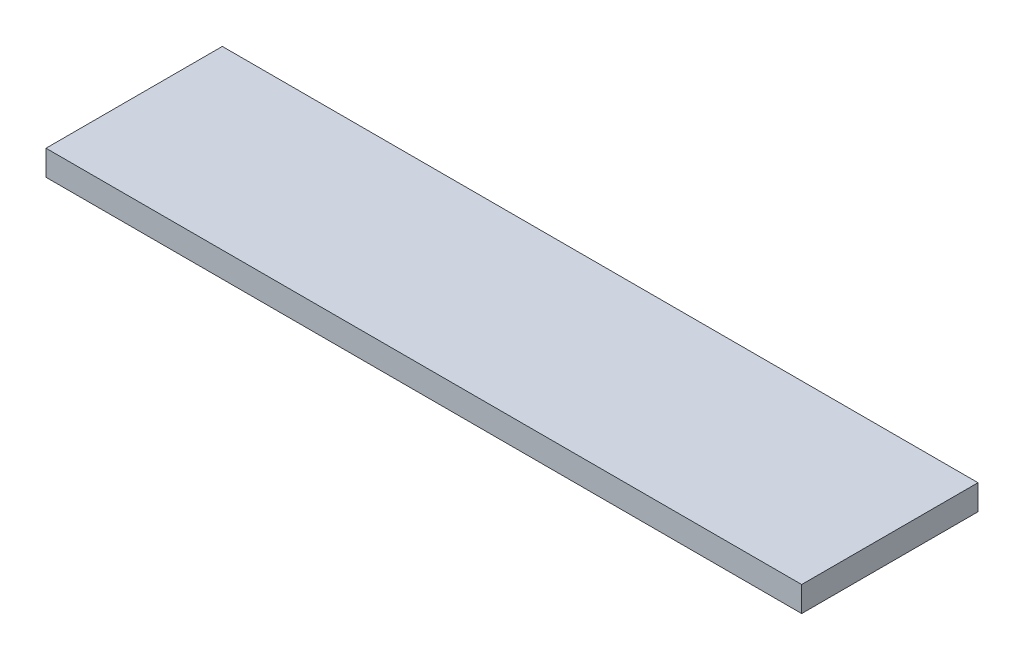
SolidWorks part; units mm, degrees
ref_plane "前视基准面" through (0, 0, 0) normal (0, 0, 1) x (1, 0, 0)
ref_plane "上视基准面" through (0, 0, 0) normal (0, 1, 0) x (1, 0, 0)
ref_plane "右视基准面" through (0, 0, 0) normal (1, 0, 0) x (0, 0, -1)
sketch "草图1" plane through (0, 0, 0) normal (0, 1, 0) x (1, 0, 0)
  line L1 (-150, 35) -> (150, 35)
  line L2 (-150, 35) -> (-150, -35)
  line L3 (-150, -35) -> (150, -35)
  line L4 (150, 35) -> (150, -35)
  line L5 (-150, 35) -> (150, -35) construction
  line L6 (-150, -35) -> (150, 35) construction
  point P0 (0, 0)
  dimension "D1" = 300
  dimension "D2" = 70
extrude "凸台-拉伸1" add sketch "草图1" along normal blind 10
